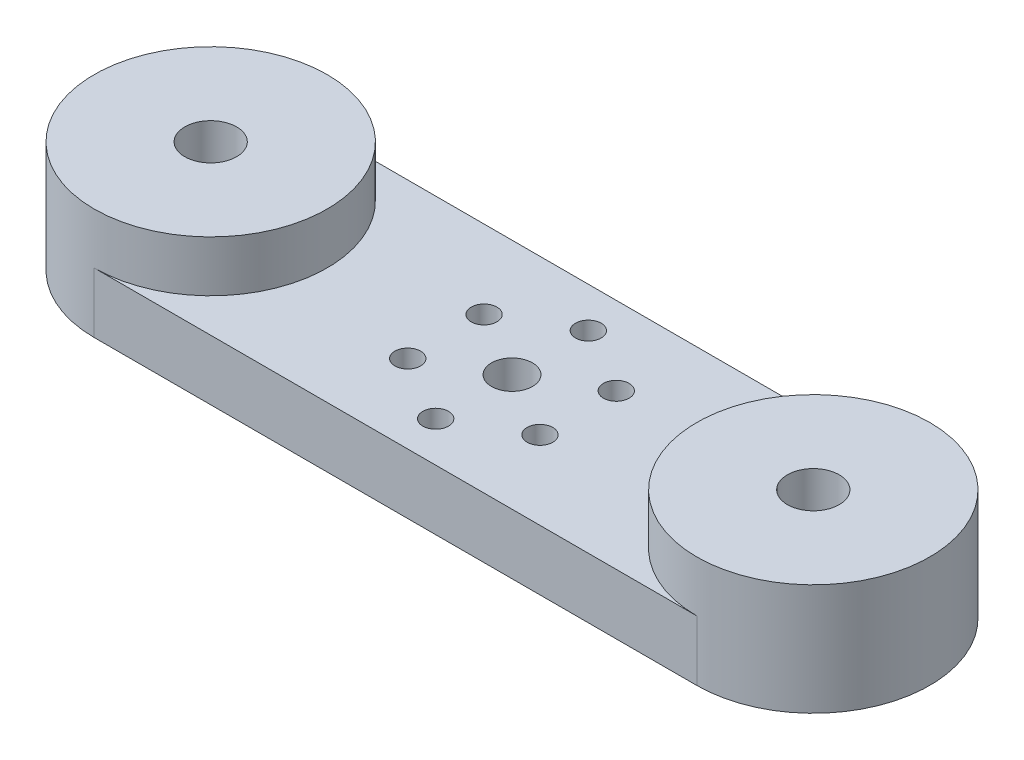
SolidWorks part; units mm, degrees
material "ABS"
ref_plane "Front Plane" through (0, 0, 0) normal (0, 0, 1) x (1, 0, 0)
ref_plane "Top Plane" through (0, 0, 0) normal (0, 1, 0) x (1, 0, 0)
ref_plane "Right Plane" through (0, 0, 0) normal (1, 0, 0) x (0, 0, -1)
sketch "Sketch1" plane through (0, 0, 0) normal (0, 1, 0) x (1, 0, 0)
  line L0 (-37.5, 0) -> (37.5, 0) construction
  line L1 (-37.5, 14.5) -> (37.5, 14.5)
  line L2 (-37.5, -14.5) -> (37.5, -14.5)
  circle A0 centre (0, 0) radius 52 construction
  circle A1 centre (0, 0) radius 9.5 construction
  circle A2 centre (0, 0) radius 2.55
  circle A3 centre (0, 9.5) radius 1.5 construction
  circle A4 centre (8.2272, 4.75) radius 1.5 construction
  circle A5 centre (8.2272, -4.75) radius 1.5 construction
  circle A6 centre (0, -9.5) radius 1.5 construction
  circle A7 centre (-8.2272, -4.75) radius 1.5 construction
  circle A8 centre (-8.2272, 4.75) radius 1.5 construction
  circle A9 centre (0, 0) radius 23 construction
  circle A10 centre (-37.5, 0) radius 3.225
  circle A11 centre (37.5, 0) radius 3.225
  circle A12 centre (-37.5, 0) radius 14.5
  circle A13 centre (37.5, 0) radius 14.5
  point P19 (0, 0)
  point P23 (0, 0)
  dimension "D1" = 5.1
  dimension "D2" = 19
  dimension "D4" = 104
  dimension "D5" = 3
  dimension "D7" = 6.45
  dimension "D8" = 75
  dimension "D3" = 6
extrude "Boss-Extrude1" add sketch "Sketch1" against normal blind 7.5 contours A12 A10 | A13 L1 A12 L2 A2 | A13 A11 | A10 | A11 region at (0, 0, -13.6959) region at (-27.537, 0, -9.963) region at (47.463, 0, -9.963) region at (-37.5, 0, 0) region at (37.5, 0, 0)
extrude "Boss-Extrude2" add sketch "Sketch1<3>" along normal blind 6.35 contours A0 A11 A10 A9 | A12 A10 region at (-27.537, 0, -9.963) region at (47.463, 0, -9.963)
sketch "Sketch1<3>" plane through (0, 0, 0) normal (0, 1, 0) x (1, 0, 0) same geometry as "Sketch1"
hole_wizard "M3 Clearance Hole1" positions "3DSketch1" profile "Sketch3" hole size "M3" standard "ANSI Metric" end condition through all
sketch3d "3DSketch1"
  point P0 (-8.2272, 0, -4.75)
  point P2 (0, 0, -9.5)
  point P4 (8.2272, 0, -4.75)
  point P6 (-8.2272, 0, 4.75)
  point P8 (8.2272, 0, 4.75)
  point P10 (0, 0, 9.5)
sketch "Sketch3" plane through (-8.2272, 0, -4.75) normal (1, 0, 0) x (0, 0, 1)
  line L0 (0, 0) -> (0, 7.5)
  line L1 (0, 7.5) -> (1.6, 7.5)
  line L2 (1.6, 7.5) -> (1.6, 0)
  line L5 (1.6, 0) -> (0, 0)
  line L11 (0, -6.35) -> (0, 107.95) construction
  dimension "Thru Hole Dia." = 3.2
  dimension "Thru Hole Depth" = 7.5
